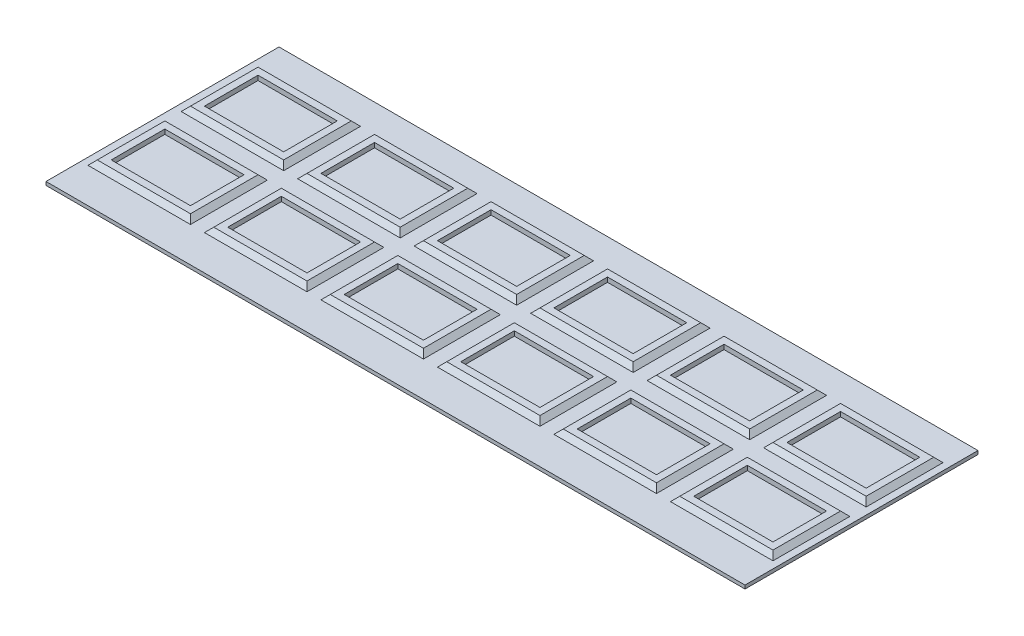
SolidWorks part; units mm, degrees
ref_plane "Front Plane" through (0, 0, 0) normal (0, 0, 1) x (1, 0, 0)
ref_plane "Top Plane" through (0, 0, 0) normal (0, 1, 0) x (1, 0, 0)
ref_plane "Right Plane" through (0, 0, 0) normal (1, 0, 0) x (0, 0, -1)
sketch "Sketch1" plane through (0, 0, 0) normal (0, 1, 0) x (1, 0, 0)
  line L1 (1500, 500) -> (-1500, 500)
  line L2 (1500, 500) -> (1500, -500)
  line L3 (1500, -500) -> (-1500, -500)
  line L4 (-1500, 500) -> (-1500, -500)
  line L5 (1500, 500) -> (-1500, -500) construction
  line L6 (1500, -500) -> (-1500, 500) construction
  point P0 (0, 0)
  dimension "D1" = 3000
  dimension "D2" = 1000
extrude "Boss-Extrude1" add sketch "Sketch1" along normal blind 15
sketch "Sketch2" plane through (0, 15, 0) normal (0, 1, 0) x (1, 0, 0)
  line L0 (-1500, 500) -> (-1500, -500) construction
  line L5 (-1420, -300) -> (-1080, -300)
  line L6 (-1420, -300) -> (-1420, -70)
  line L7 (-1420, -70) -> (-1080, -70)
  line L8 (-1080, -300) -> (-1080, -70)
  line L9 (-1420, -300) -> (-1080, -70) construction
  line L10 (-1420, -70) -> (-1080, -300) construction
  line L11 (-1500, -500) -> (1500, -500) construction
  line L13 (-1050, -330) -> (-1450, -330)
  line L14 (-1050, -330) -> (-1050, -40)
  line L15 (-1050, -40) -> (-1450, -40)
  line L16 (-1450, -330) -> (-1450, -40)
  line L17 (-1050, -330) -> (-1450, -40) construction
  line L18 (-1050, -40) -> (-1450, -330) construction
  point P0 (-1250, -185)
  point P9 (-1250, -185)
  dimension "D1" = 340
  dimension "D2" = 230
  dimension "D3" = 80
  dimension "D4" = 200
  dimension "D5" = 30
  dimension "D6" = 30
extrude "Boss-Extrude2" add sketch "Sketch2" along normal blind 20
chamfer "Chamfer1" distance 20 angle 45 4 edges at (-1450, 15, 185) (-1050, 15, 185) (-1250, 15, 330) (-1250, 15, 40)
pattern_linear "LPattern1" count 6 spacing 500 along (1, 0, 0) count 2 spacing 400 along (0, 0, -1) of "Boss-Extrude2", "Chamfer1"
